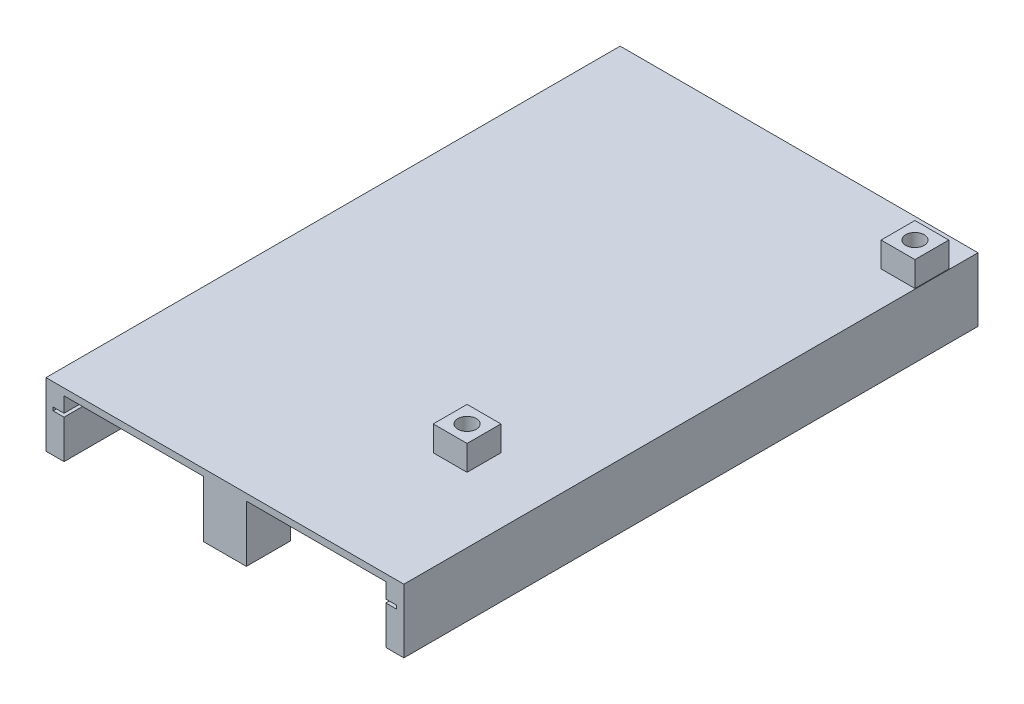
SolidWorks part; units mm, degrees
material "PLA"
ref_plane "Спереди" through (0, 0, 0) normal (0, 0, 1) x (1, 0, 0)
ref_plane "Сверху" through (0, 0, 0) normal (0, 1, 0) x (1, 0, 0)
ref_plane "Справа" through (0, 0, 0) normal (1, 0, 0) x (0, 0, -1)
sketch "Эскиз1" plane through (0, 0, 0) normal (0, 1, 0) x (1, 0, 0)
  line L0 (0, 0) -> (-4740.9496, 0) construction
  line L1 (0, 0) -> (0, -4740.9496) construction
  line L2 (35.675, 63.65) -> (39.675, 63.65)
  line L3 (-35.675, -63.65) -> (-39.675, -63.65)
  line L4 (-35.675, -63.65) -> (-35.675, 63.65)
  line L5 (-35.675, 63.65) -> (-39.675, 63.65)
  line L6 (-39.675, -63.65) -> (-39.675, 63.65)
  line L7 (-35.675, -63.65) -> (-39.675, 63.65) construction
  line L8 (-35.675, 63.65) -> (-39.675, -63.65) construction
  line L9 (39.675, -63.65) -> (39.675, 63.65)
  line L10 (35.675, -63.65) -> (39.675, -63.65)
  line L11 (35.675, -63.65) -> (35.675, 63.65)
  line L12 (35.675, 63.65) -> (39.675, -63.65) construction
  line L13 (35.675, -63.65) -> (39.675, 63.65) construction
  point P5 (-37.675, 0)
  point P14 (37.675, 0)
  dimension "D1" = 4
  dimension "D2" = 127.3
  dimension "D3" = 71.35
extrude "Бобышка-Вытянуть1" add sketch "Эскиз1" along normal blind 12.65
sketch "Эскиз2" plane through (0, 12.65, 0) normal (0, 1, 0) x (1, 0, 0)
  line L1 (39.675, 63.65) -> (-39.675, 63.65)
  line L2 (39.675, 63.65) -> (39.675, -63.65)
  line L3 (39.675, -63.65) -> (-39.675, -63.65)
  line L4 (-39.675, 63.65) -> (-39.675, -63.65)
extrude "Бобышка-Вытянуть2" add sketch "Эскиз2" along normal blind 1.5
sketch "Эскиз3" plane through (0, 0, -63.65) normal (0, 0, -1) x (-1, 0, 0)
  line L0 (0, 0) -> (0, 50000) construction
  line L1 (-35.675, 12.65) -> (-35.675, 0) construction
  line L2 (-35.675, 9.3) -> (-38.075, 9.3)
  line L3 (-35.675, 9.3) -> (-35.675, 8.55)
  line L4 (-35.675, 8.55) -> (-38.075, 8.55)
  line L5 (-38.075, 9.3) -> (-38.075, 8.55)
  line L6 (35.675, 8.55) -> (38.075, 8.55)
  line L7 (38.075, 9.3) -> (38.075, 8.55)
  line L8 (35.675, 9.3) -> (38.075, 9.3)
  line L9 (35.675, 9.3) -> (35.675, 8.55)
  line L10 (-39.675, 0) -> (-35.675, 0) construction
  dimension "D1" = 2.4
  dimension "D2" = 0.75
  dimension "D3" = 8.55
extrude "Вырез-Вытянуть1" cut sketch "Эскиз3" against normal through all from offset 1.5 offset against normal yes
sketch "Эскиз4" plane through (0, 12.65, 0) normal (0, -1, 0) x (1, 0, 0)
  line L0 (35.675, -63.65) -> (35.675, 63.65) construction
  line L1 (-35.675, -63.65) -> (35.675, -63.65)
  line L2 (-35.675, -63.65) -> (-35.675, -62.15)
  line L3 (-35.675, -62.15) -> (35.675, -62.15)
  line L4 (35.675, -63.65) -> (35.675, -62.15)
  dimension "D1" = 1.5
extrude "Бобышка-Вытянуть3" add sketch "Эскиз4" along normal up to surface (12.65 mm away) up to face at (37.675, 0, 0)
sketch "Эскиз6" plane through (0, 12.65, 0) normal (0, -1, 0) x (1, 0, 0)
  line L0 (35.675, -62.15) -> (35.675, 63.65) construction
  line L1 (32.325, -52.35) -> (24.825, -52.35)
  line L2 (32.325, -52.35) -> (32.325, -62.15)
  line L3 (32.325, -59.85) -> (24.825, -59.85) construction
  line L4 (24.825, -52.35) -> (24.825, -62.15)
  line L5 (32.325, -52.35) -> (24.825, -59.85) construction
  line L6 (32.325, -59.85) -> (24.825, -52.35) construction
  line L7 (35.675, -62.15) -> (-35.675, -62.15) construction
  line L8 (32.325, -62.15) -> (24.825, -62.15)
  circle A0 centre (28.575, -56.1) radius 2.1 construction
  point P0 (28.575, -56.1)
  dimension "D3" = 4.2
  dimension "D4" = 1.65
  dimension "D5" = 1.65
  dimension "D1" = 7.1
  dimension "D2" = 6.05
extrude "Бобышка-Вытянуть5" add sketch "Эскиз6" along normal blind 9.6
sketch "Эскиз7" plane through (0, 3.05, 0) normal (0, -1, 0) x (1, 0, 0)
  line L0 (24.825, -52.35) -> (32.325, -59.85) construction
  line L1 (32.325, -52.35) -> (24.825, -59.85) construction
  line L2 (32.325, -62.15) -> (32.325, -52.35) construction
  line L3 (24.825, -52.35) -> (24.825, -62.15) construction
  circle A0 centre (28.575, -56.1) radius 2.05
  dimension "D1" = 4.1
extrude "Вырез-Вытянуть2" cut sketch "Эскиз7" against normal blind 4.5
sketch "Эскиз8" plane through (0, 0, 0) normal (0, -1, 0) x (1, 0, 0)
  line L0 (-35.675, 63.65) -> (-35.675, -62.15) construction
  line L1 (-35.675, 36.4) -> (-38.075, 36.4)
  line L2 (-35.675, 36.4) -> (-35.675, 30.55)
  line L3 (-35.675, 30.55) -> (-38.075, 30.55)
  line L4 (-38.075, 36.4) -> (-38.075, 30.55)
  line L5 (0, 0) -> (0, 50000) construction
  line L6 (-35.675, -18.2) -> (-38.075, -18.2)
  line L7 (-35.675, -18.2) -> (-35.675, -24.05)
  line L8 (-35.675, -24.05) -> (-38.075, -24.05)
  line L9 (-38.075, -18.2) -> (-38.075, -24.05)
  line L10 (-39.675, 63.65) -> (-35.675, 63.65) construction
  line L11 (35.675, -24.05) -> (38.075, -24.05)
  line L12 (38.075, -18.2) -> (38.075, -24.05)
  line L13 (35.675, -18.2) -> (38.075, -18.2)
  line L14 (35.675, -18.2) -> (35.675, -24.05)
  line L15 (35.675, 30.55) -> (38.075, 30.55)
  line L16 (38.075, 36.4) -> (38.075, 30.55)
  line L17 (35.675, 36.4) -> (38.075, 36.4)
  line L18 (35.675, 36.4) -> (35.675, 30.55)
  line L19 (39.675, -63.65) -> (-39.675, -63.65) construction
  point P26 (0, -63.65)
  dimension "D1" = 2.4
  dimension "D2" = 5.85
  dimension "D3" = 48.75
  dimension "D4" = 27.25
extrude "Вырез-Вытянуть3" cut sketch "Эскиз8" against normal up to surface (8.55 mm away) up to face at (-36.875, 8.55, 0.75)
sketch "Эскиз10" plane through (0, 12.65, 0) normal (0, -1, 0) x (1, 0, 0)
  line L0 (-35.675, 63.65) -> (-35.675, -62.15) construction
  line L1 (-25.275, -51.75) -> (-28.275, -51.75)
  line L2 (-25.275, -51.75) -> (-25.275, -57.7)
  line L3 (-25.275, -57.7) -> (-28.275, -57.7)
  line L4 (-28.275, -51.75) -> (-28.275, -57.7)
  line L5 (24.825, -62.15) -> (-35.675, -62.15) construction
  line L6 (35.675, -62.15) -> (-35.675, -62.15) construction
  line L8 (15.225, -51.75) -> (18.225, -51.75)
  line L9 (15.225, -51.75) -> (15.225, -57.7)
  line L10 (15.225, -57.7) -> (18.225, -57.7)
  line L11 (18.225, -51.75) -> (18.225, -57.7)
  dimension "D1" = 10.4
  dimension "D2" = 4.45
  dimension "D3" = 10.4
  dimension "D4" = 3
  dimension "D5" = 50.9
extrude "Бобышка-Вытянуть6" add sketch "Эскиз10" along normal blind 3.95
sketch "Эскиз11" plane through (0, 12.65, 0) normal (0, -1, 0) x (1, 0, 0)
  line L1 (-25.275, -57.7) -> (15.225, -57.7)
  line L2 (-25.275, -57.7) -> (-25.275, -51.75)
  line L3 (-25.275, -51.75) -> (15.225, -51.75)
  line L4 (15.225, -57.7) -> (15.225, -51.75)
extrude "Бобышка-Вытянуть7" add sketch "Эскиз11" along normal blind 0.35
fillet "Скругление4" radius 4 1 edges at (-5.025, 12.65, -57.7)
fillet "Скругление5" radius 2 2 edges at (-26.775, 8.7, -57.7) (16.725, 8.7, -57.7)
sketch "Эскиз12" plane through (0, 0, -62.15) normal (0, 0, 1) x (1, 0, 0)
  line L0 (24.825, 12.65) -> (-35.675, 12.65) construction
  line L1 (15.475, 8) -> (-25.525, 8)
  line L2 (15.475, 8) -> (15.475, 12.65)
  line L12 (15.475, 12.65) -> (-25.525, 12.65)
  line L13 (-25.525, 8) -> (-25.525, 12.65)
  line L15 (-5.025, 12.3) -> (-5.025, 12.65) construction
  line L17 (-25.275, 12.3) -> (15.225, 12.3) construction
  point P13 (-5.025, 12.3)
  dimension "D1" = 4.65
  dimension "D2" = 41
extrude "Вырез-Вытянуть4" cut sketch "Эскиз12" against normal through all
sketch "Эскиз13" plane through (0, 12.65, 0) normal (0, -1, 0) x (1, 0, 0)
  line L0 (0, 63.65) -> (0, 50063.65) construction
  line L1 (-35.675, 63.65) -> (35.675, 63.65) construction
  line L2 (-4.75, 63.4) -> (-4.75, 63.65)
  line L3 (4.75, 63.4) -> (-4.75, 63.4) construction
  line L4 (4.75, 63.4) -> (4.75, 53.9)
  line L5 (4.75, 53.9) -> (-4.75, 53.9)
  line L6 (-4.75, 63.4) -> (-4.75, 53.9)
  line L7 (4.75, 63.4) -> (-4.75, 53.9) construction
  line L8 (4.75, 53.9) -> (-4.75, 63.4) construction
  line L9 (-4.75, 63.65) -> (4.75, 63.65)
  line L10 (4.75, 63.65) -> (4.75, 63.4)
  circle A0 centre (0, 58.65) radius 2.75 construction
  point P4 (0, 63.65)
  point P5 (0, 58.65)
  dimension "D1" = 5.5
  dimension "D2" = 9.5
  dimension "D3" = 5
  dimension "D4" = 0.25
extrude "Бобышка-Вытянуть8" add sketch "Эскиз13" along normal blind 12.55
sketch "Эскиз14" plane through (0, 0.1, 0) normal (0, -1, 0) x (1, 0, 0)
  line L0 (-4.75, 63.4) -> (4.75, 53.9) construction
  line L1 (4.75, 63.4) -> (-4.75, 53.9) construction
  line L2 (4.75, 53.9) -> (4.75, 63.65) construction
  line L3 (-4.75, 63.65) -> (-4.75, 53.9) construction
  line L4 (-4.75, 63.4) -> (4.75, 63.4) construction
  circle A0 centre (0, 58.65) radius 2.05
  dimension "D1" = 4.1
extrude "Вырез-Вытянуть5" cut sketch "Эскиз14" against normal blind 7
sketch "Эскиз15" plane through (0, 14.15, 0) normal (0, 1, 0) x (1, 0, 0)
  line L0 (39.675, -63.65) -> (39.675, 63.65) construction
  line L1 (32.0454, 57.2971) -> (39.5454, 57.2971)
  line L2 (32.0454, 57.2971) -> (32.0454, 49.7971)
  line L3 (32.0454, 49.7971) -> (39.5454, 49.7971)
  line L4 (39.5454, 57.2971) -> (39.5454, 49.7971)
  line L5 (32.0454, 57.2971) -> (39.5454, 49.7971) construction
  line L6 (32.0454, 49.7971) -> (39.5454, 57.2971) construction
  line L7 (17.7005, -27.6612) -> (25.2005, -27.6612)
  line L8 (17.7005, -27.6612) -> (17.7005, -35.1612)
  line L9 (17.7005, -35.1612) -> (25.2005, -35.1612)
  line L10 (25.2005, -27.6612) -> (25.2005, -35.1612)
  line L11 (17.7005, -27.6612) -> (25.2005, -35.1612) construction
  line L12 (17.7005, -35.1612) -> (25.2005, -27.6612) construction
  line L13 (-39.675, -63.65) -> (39.675, -63.65) construction
  point P0 (35.7954, 53.5471)
  point P5 (21.4505, -31.4112)
  dimension "D1" = 7.5
  dimension "D2" = 18.2245
  dimension "D3" = 32.2388
  dimension "D4" = 3.8796
  dimension "D5" = 117.1971
extrude "Бобышка-Вытянуть9" add sketch "Эскиз15" along normal blind 5.55
sketch "Эскиз16" plane through (0, 19.7, 0) normal (0, 1, 0) x (1, 0, 0)
  line L0 (32.0454, 57.2971) -> (39.5454, 49.7971) construction
  line L1 (39.5454, 57.2971) -> (32.0454, 49.7971) construction
  line L2 (25.2005, -27.6612) -> (17.7005, -35.1612) construction
  line L3 (17.7005, -27.6612) -> (25.2005, -35.1612) construction
  circle A0 centre (21.4505, -31.4112) radius 2.05
  circle A1 centre (35.7954, 53.5471) radius 2.05
  dimension "D1" = 4.1
extrude "Вырез-Вытянуть6" cut sketch "Эскиз16" against normal blind 5
